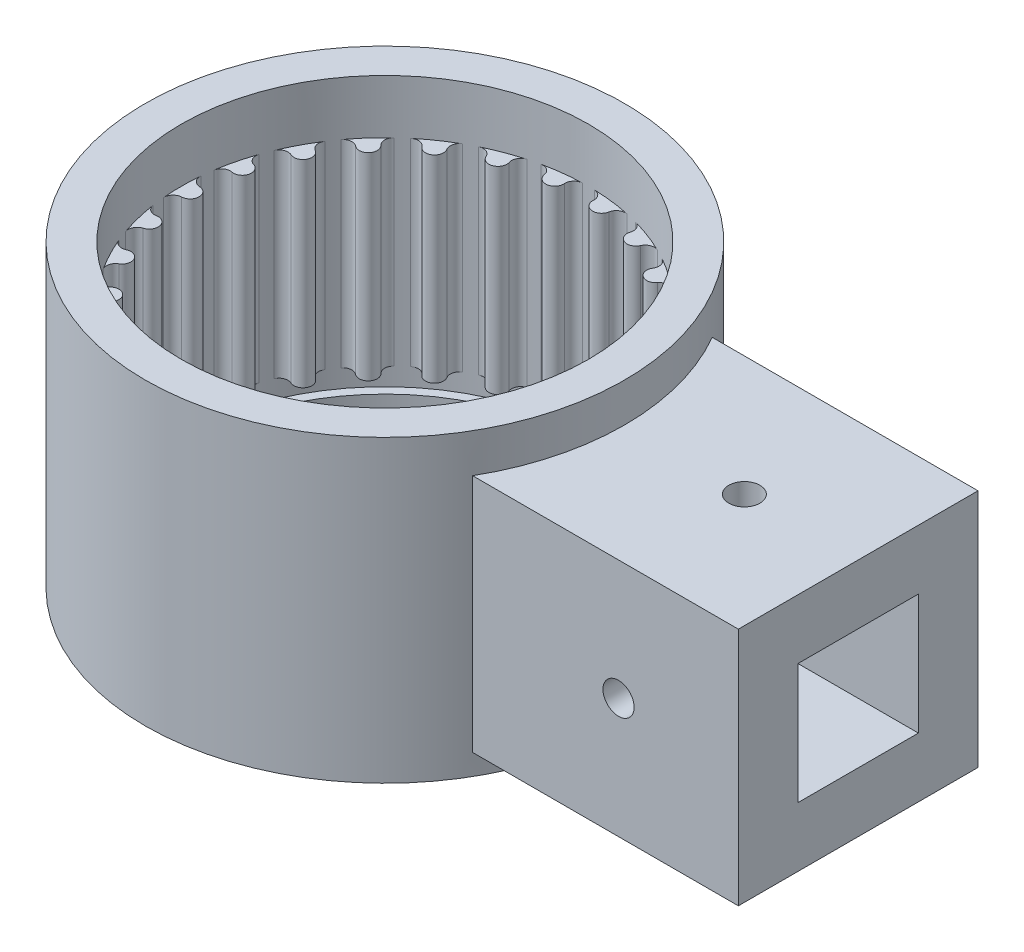
SolidWorks part; units mm, degrees
ref_plane "Front Plane" through (0, 0, 0) normal (0, 0, 1) x (1, 0, 0)
ref_plane "Top Plane" through (0, 0, 0) normal (0, 1, 0) x (1, 0, 0)
ref_plane "Right Plane" through (0, 0, 0) normal (1, 0, 0) x (0, 0, -1)
sketch "Sketch1" plane through (0, 0, 0) normal (0, 1, 0) x (1, 0, 0)
  circle A0 centre (0, 0) radius 34
  circle A1 centre (0, 0) radius 40
  dimension "D1" = 68
  dimension "D2" = 80
extrude "Boss-Extrude1" add sketch "Sketch1" along normal blind 50
ref_plane "Plane1" through (0, 41, 0) normal (0, 1, 0) x (1, 0, 0)
sketch "Sketch3" plane through (0, 41, 0) normal (0, 1, 0) x (1, 0, 0)
  circle A0 centre (0, 0) radius 34
  circle A1 centre (0, 0) radius 32.5 construction
  arc A2 (32.4654, 1.4996) -> (32.4654, -1.4996) centre (32.5, 0) ccw
  arc A3 (33.8551, -3.1351) -> (32.4308, -1.4984) centre (32.3615, -2.9968) ccw
  arc A4 (32.4308, 1.4984) -> (33.8551, 3.1351) centre (32.3615, 2.9968) ccw
  arc A5 (31.847, -6.3063) -> (33.6217, -5.0581) centre (32.1384, -4.8349) ccw
  arc A6 (31.8809, -6.3135) -> (31.1631, -9.2255) centre (31.5556, -7.7778) ccw
  arc A7 (32.1211, -11.1461) -> (31.1298, -9.2161) centre (30.704, -10.6543) ccw
  arc A8 (29.4124, -13.7446) -> (31.4342, -12.9573) centre (30.0474, -12.3856) ccw
  arc A9 (29.4436, -13.7596) -> (28.0498, -16.4152) centre (28.7773, -15.1035) ccw
  arc A10 (28.5203, -18.5093) -> (28.0197, -16.3981) centre (27.262, -17.6927) ccw
  arc A11 (25.2684, -20.384) -> (27.4199, -20.1034) centre (26.2102, -19.2165) ccw
  arc A12 (25.2951, -20.4061) -> (23.3063, -22.651) centre (24.3266, -21.5515) ccw
  arc A13 (23.262, -24.7968) -> (23.2812, -22.6271) centre (22.2357, -23.7028) ccw
  arc A14 (19.6559, -25.8388) -> (21.8121, -26.0813) centre (20.8498, -24.9306) ccw
  arc A15 (19.6766, -25.8666) -> (17.2083, -27.5704) centre (18.4621, -26.747) ccw
  arc A16 (16.6518, -29.6432) -> (17.1896, -27.5412) centre (15.9171, -28.3354) ccw
  arc A17 (12.9011, -29.792) -> (14.9366, -30.5434) centre (14.2776, -29.1959) ccw
  arc A18 (12.9145, -29.8239) -> (10.1102, -30.8874) centre (11.5247, -30.388) ccw
  arc A19 (9.0738, -32.7668) -> (10.0991, -30.8546) centre (8.6735, -31.3212) ccw
  arc A20 (5.3966, -32.0137) -> (7.193, -33.2304) centre (6.8757, -31.7644) ccw
  arc A21 (5.4019, -32.0479) -> (2.4246, -32.4094) centre (3.9174, -32.263) ccw
  arc A22 (0.9685, -33.9862) -> (2.4216, -32.3749) centre (0.9258, -32.4868) ccw
  arc A23 (-2.4216, -32.3749) -> (-0.9685, -33.9862) centre (-0.9258, -32.4868) ccw
  arc A24 (-2.4246, -32.4094) -> (-5.4019, -32.0479) centre (-3.9174, -32.263) ccw
  arc A25 (-7.193, -33.2304) -> (-5.3966, -32.0137) centre (-6.8757, -31.7644) ccw
  arc A26 (-10.0991, -30.8546) -> (-9.0738, -32.7668) centre (-8.6735, -31.3212) ccw
  arc A27 (-10.1102, -30.8874) -> (-12.9145, -29.8239) centre (-11.5247, -30.388) ccw
  arc A28 (-14.9366, -30.5434) -> (-12.9011, -29.792) centre (-14.2776, -29.1959) ccw
  arc A29 (-17.1896, -27.5412) -> (-16.6518, -29.6432) centre (-15.9171, -28.3354) ccw
  arc A30 (-17.2083, -27.5704) -> (-19.6766, -25.8666) centre (-18.4621, -26.747) ccw
  arc A31 (-21.8121, -26.0813) -> (-19.6559, -25.8388) centre (-20.8498, -24.9306) ccw
  arc A32 (-23.2812, -22.6271) -> (-23.262, -24.7968) centre (-22.2357, -23.7028) ccw
  arc A33 (-23.3063, -22.651) -> (-25.2951, -20.4061) centre (-24.3266, -21.5515) ccw
  arc A34 (-27.4199, -20.1034) -> (-25.2684, -20.384) centre (-26.2102, -19.2165) ccw
  arc A35 (-28.0197, -16.3981) -> (-28.5203, -18.5093) centre (-27.262, -17.6927) ccw
  arc A36 (-28.0498, -16.4152) -> (-29.4436, -13.7596) centre (-28.7773, -15.1035) ccw
  arc A37 (-31.4342, -12.9573) -> (-29.4124, -13.7446) centre (-30.0474, -12.3856) ccw
  arc A38 (-31.1298, -9.2161) -> (-32.1211, -11.1461) centre (-30.704, -10.6543) ccw
  arc A39 (-31.1631, -9.2255) -> (-31.8809, -6.3135) centre (-31.5556, -7.7778) ccw
  arc A40 (-33.6217, -5.0581) -> (-31.847, -6.3063) centre (-32.1384, -4.8349) ccw
  arc A41 (-32.4308, -1.4984) -> (-33.8551, -3.1351) centre (-32.3615, -2.9968) ccw
  arc A42 (-32.4654, -1.4996) -> (-32.4654, 1.4996) centre (-32.5, 0) ccw
  arc A43 (-33.8551, 3.1351) -> (-32.4308, 1.4984) centre (-32.3615, 2.9968) ccw
  arc A44 (-31.847, 6.3063) -> (-33.6217, 5.0581) centre (-32.1384, 4.8349) ccw
  arc A45 (-31.8809, 6.3135) -> (-31.1631, 9.2255) centre (-31.5556, 7.7778) ccw
  arc A46 (-32.1211, 11.1461) -> (-31.1298, 9.2161) centre (-30.704, 10.6543) ccw
  arc A47 (-29.4124, 13.7446) -> (-31.4342, 12.9573) centre (-30.0474, 12.3856) ccw
  arc A48 (-29.4436, 13.7596) -> (-28.0498, 16.4152) centre (-28.7773, 15.1035) ccw
  arc A49 (-28.5203, 18.5093) -> (-28.0197, 16.3981) centre (-27.262, 17.6927) ccw
  arc A50 (-25.2684, 20.384) -> (-27.4199, 20.1034) centre (-26.2102, 19.2165) ccw
  arc A51 (-25.2951, 20.4061) -> (-23.3063, 22.651) centre (-24.3266, 21.5515) ccw
  arc A52 (-23.262, 24.7968) -> (-23.2812, 22.6271) centre (-22.2357, 23.7028) ccw
  arc A53 (-19.6559, 25.8388) -> (-21.8121, 26.0813) centre (-20.8498, 24.9306) ccw
  arc A54 (-19.6766, 25.8666) -> (-17.2083, 27.5704) centre (-18.4621, 26.747) ccw
  arc A55 (-16.6518, 29.6432) -> (-17.1896, 27.5412) centre (-15.9171, 28.3354) ccw
  arc A56 (-12.9011, 29.792) -> (-14.9366, 30.5434) centre (-14.2776, 29.1959) ccw
  arc A57 (-12.9145, 29.8239) -> (-10.1102, 30.8874) centre (-11.5247, 30.388) ccw
  arc A58 (-9.0738, 32.7668) -> (-10.0991, 30.8546) centre (-8.6735, 31.3212) ccw
  arc A59 (-5.3966, 32.0137) -> (-7.193, 33.2304) centre (-6.8757, 31.7644) ccw
  arc A60 (-5.4019, 32.0479) -> (-2.4246, 32.4094) centre (-3.9174, 32.263) ccw
  arc A61 (-0.9685, 33.9862) -> (-2.4216, 32.3749) centre (-0.9258, 32.4868) ccw
  arc A62 (2.4216, 32.3749) -> (0.9685, 33.9862) centre (0.9258, 32.4868) ccw
  arc A63 (2.4246, 32.4094) -> (5.4019, 32.0479) centre (3.9174, 32.263) ccw
  arc A64 (7.193, 33.2304) -> (5.3966, 32.0137) centre (6.8757, 31.7644) ccw
  arc A65 (10.0991, 30.8546) -> (9.0738, 32.7668) centre (8.6735, 31.3212) ccw
  arc A66 (10.1102, 30.8874) -> (12.9145, 29.8239) centre (11.5247, 30.388) ccw
  arc A67 (14.9366, 30.5434) -> (12.9011, 29.792) centre (14.2776, 29.1959) ccw
  arc A68 (17.1896, 27.5412) -> (16.6518, 29.6432) centre (15.9171, 28.3354) ccw
  arc A69 (17.2083, 27.5704) -> (19.6766, 25.8666) centre (18.4621, 26.747) ccw
  arc A70 (21.8121, 26.0813) -> (19.6559, 25.8388) centre (20.8498, 24.9306) ccw
  arc A71 (23.2812, 22.6271) -> (23.262, 24.7968) centre (22.2357, 23.7028) ccw
  arc A72 (23.3063, 22.651) -> (25.2951, 20.4061) centre (24.3266, 21.5515) ccw
  arc A73 (27.4199, 20.1034) -> (25.2684, 20.384) centre (26.2102, 19.2165) ccw
  arc A74 (28.0197, 16.3981) -> (28.5203, 18.5093) centre (27.262, 17.6927) ccw
  arc A75 (28.0498, 16.4152) -> (29.4436, 13.7596) centre (28.7773, 15.1035) ccw
  arc A76 (31.4342, 12.9573) -> (29.4124, 13.7446) centre (30.0474, 12.3856) ccw
  arc A77 (31.1298, 9.2161) -> (32.1211, 11.1461) centre (30.704, 10.6543) ccw
  arc A78 (31.1631, 9.2255) -> (31.8809, 6.3135) centre (31.5556, 7.7778) ccw
  arc A79 (33.6217, 5.0581) -> (31.847, 6.3063) centre (32.1384, 4.8349) ccw
  point P241 (0, 0)
  dimension "D1" = 68
  dimension "D2" = 65
  dimension "D3" = 3
  dimension "D4" = 3
extrude "Boss-Extrude2" add sketch "Sketch3" against normal blind 33 contours A28 A0 A26 A27 | A31 A0 A29 A30 | A34 A0 A32 A33 | A37 A0 A35 A36 | A40 A0 A38 A39 | A43 A0 A41 A42 | A46 A0 A44 A45 | A49 A0 A47 A48 | A52 A0 A50 A51 | A55 A0 A53 A54 | A58 A0 A56 A57 | A61 A0 A59 A60 | A64 A0 A62 A63 | A67 A0 A65 A66 | A70 A0 A68 A69 | A73 A0 A71 A72 | A76 A0 A74 A75 | A79 A0 A77 A78 | A4 A2 A3 A0 | A7 A0 A5 A6 | A10 A0 A8 A9 | A13 A0 A11 A12 | A16 A0 A14 A15 | A19 A0 A17 A18 | A25 A0 A23 A24 | A22 A0 A20 A21 region at (32.7536, 41, 0) region at (31.8018, 41, -7.8385) region at (31.8018, 41, 7.8385) region at (29.0019, 41, -15.2214) region at (29.0019, 41, 15.2214) region at (24.5164, 41, -21.7197) region at (24.5164, 41, 21.7197) region at (18.6062, 41, -26.9557) region at (18.6062, 41, 26.9557) region at (11.6146, 41, -30.6252) region at (11.6146, 41, 30.6252) region at (3.948, 41, -32.5148) region at (3.948, 41, 32.5148) region at (-3.948, 41, -32.5148) region at (-3.948, 41, 32.5148) region at (-11.6146, 41, -30.6252) region at (-11.6146, 41, 30.6252) region at (-18.6062, 41, -26.9557) region at (-18.6062, 41, 26.9557) region at (-24.5164, 41, -21.7197) region at (-24.5164, 41, 21.7197) region at (-29.0019, 41, -15.2214) region at (-29.0019, 41, 15.2214) region at (-31.8018, 41, -7.8385) region at (-31.8018, 41, 7.8385) region at (-32.7536, 41, 0)
ref_plane "Plane2" through (79, 0, 0) normal (1, 0, 0) x (0, 0, -1)
sketch "Sketch5" plane through (79, 0, 0) normal (1, 0, 0) x (0, 0, -1)
  line L0 (0, 0) -> (0, 23.5) construction
  line L2 (-20, 43.5) -> (20, 43.5)
  line L3 (-20, 43.5) -> (-20, 3.5)
  line L4 (-20, 3.5) -> (20, 3.5)
  line L5 (20, 43.5) -> (20, 3.5)
  line L6 (-20, 43.5) -> (20, 3.5) construction
  line L7 (-20, 3.5) -> (20, 43.5) construction
  line L8 (10.05, 13.45) -> (-10.05, 13.45)
  line L9 (10.05, 13.45) -> (10.05, 33.55)
  line L10 (10.05, 33.55) -> (-10.05, 33.55)
  line L11 (-10.05, 13.45) -> (-10.05, 33.55)
  line L12 (10.05, 13.45) -> (-10.05, 33.55) construction
  line L13 (10.05, 33.55) -> (-10.05, 13.45) construction
  dimension "D1" = 23.5
  dimension "D2" = 40
  dimension "D3" = 40
  dimension "D4" = 20.1
extrude "Boss-Extrude3" add sketch "Sketch5" against normal up to surface (44.359 mm away) up to face at (0, 50, 40)
sketch "Sketch6" plane through (0, 43.5, 0) normal (0, 1, 0) x (1, 0, 0)
  line L0 (0, 0) -> (60, 0) construction
  circle A0 centre (60, 0) radius 2.6
  dimension "D2" = 5.2
  dimension "D1" = 60
extrude "Cut-Extrude1" cut sketch "Sketch6" against normal through all
sketch "Sketch8" plane through (0, 0, 20) normal (0, 0, 1) x (1, 0, 0)
  line L0 (79, 3.5) -> (79, 23.5) construction
  line L1 (79, 43.5) -> (79, 3.5) construction
  line L2 (79, 23.5) -> (59, 23.5) construction
  circle A0 centre (59, 23.5) radius 2.6
  dimension "D2" = 5.2
  dimension "D1" = 20
extrude "Cut-Extrude2" cut sketch "Sketch8" against normal through all
ref_plane "Plane3" through (0, 1, 0) normal (0, -1, 0) x (-1, 0, 0)
sketch "Sketch10" plane through (0, 0, 0) normal (0, -1, 0) x (-1, 0, 0)
  circle A0 centre (0, 0) radius 40
  circle A1 centre (0, 0) radius 32.5
  dimension "D1" = 80
  dimension "D2" = 65
extrude "Boss-Extrude4" add sketch "Sketch10" against normal blind 5
